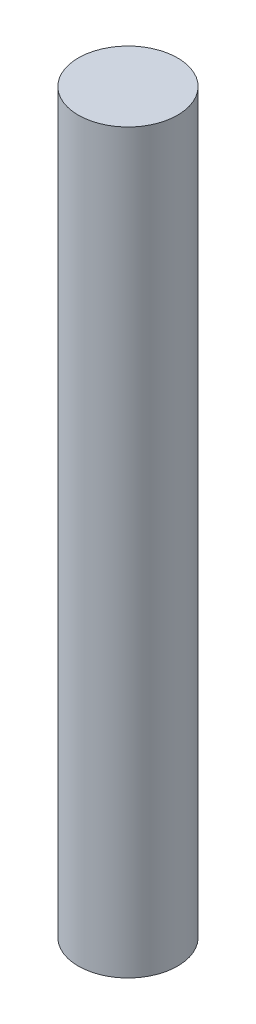
SolidWorks part; units mm, degrees
ref_plane "Front Plane" through (0, 0, 0) normal (0, 0, 1) x (1, 0, 0)
ref_plane "Top Plane" through (0, 0, 0) normal (0, 1, 0) x (1, 0, 0)
ref_plane "Right Plane" through (0, 0, 0) normal (1, 0, 0) x (0, 0, -1)
sketch "Sketch1" plane through (0, 0, 0) normal (0, 1, 0) x (1, 0, 0)
  circle A0 centre (0, 0) radius 27
  dimension "D1" = 54
extrude "Boss-Extrude1" add sketch "Sketch1" along normal blind 401
equation "\"Motor_Length\" = 401mm"
equation "\"Motor_OD\" = 54mm"
equation "\"D1@Sketch1\"=\"Motor_OD\""
equation "\"D1@Boss-Extrude1\"=\"Motor_Length\""
equation "\"Aft_Section_Length\" = 32in"
equation "\"Mid_Coupler_Length\" = 12in"
equation "\"AB_Coupler_OD_Length\"= 1in"
equation "\"AB_Coupling_Section_Length\"= 0.375in"
equation "\"AB_Coupler_Length\"= \"AB_Coupler_OD_Length\" + \"AB_Coupling_Section_Length\" * 2"
equation "\"Cutout_Angle\" = 60"
equation "\"AB_Paddle_Height\" = 0.375in"
equation "\"AB_Coupler_Num_Screws\"= 4"
equation "\"Num_Cutouts\" = 4"
equation "\"AB_Coupler_OD\"= 4.024in"
equation "\"AB_Coupler_ID\"= 3.7in"
equation "\"AB_Coupler_Surface_Diameter\"= 3.899in"
equation "\"AB_Coupling_Screw_Diameter\"= 0.1065in"
equation "\"AB_Central_Bushing_Length\" = 0.75in"
equation "\"Lead_Screw_Dist\" = 2in"
equation "\"Lead_Screw_Diam\" = 0.375in"
equation "\"Lead_Screw_Length\" = \"Mid_Coupler_Length\" + 2*0.375in + 2*0.5in"
equation "\"Paddle_Pin_Offset\" = 0.25in"
equation "\"Paddle_Pin_Radius\" = 2.25*2/3in"
equation "\"Paddle_Gear_OD\" = 3.2in"
equation "\"Fwd_BKHD_From_Top\" = 18in"
equation "\"Body_Tube_OD\"= 4.024in"
equation "\"Body_Tube_ID\"= 3.90in"
equation "\"Coupler_OD\" = 3.899in"
equation "\"Coupler_ID\" = 3.755in"
equation "\"Fwd_Section_Length\" = 20in"
equation "\"Mid_Section_Length\" = 4in"
equation "\"Aft_Upper_Tube_Length\" = 10in"
equation "\"Aft_Lower_Tube_Length\" = 18in"
equation "\"Nosecone_Coupler_Length\" = 5in"
equation "\"Avionics_Bulkhead_Thickness\" = 0.25in"
equation "\"Avionics_Bulkhead_Lip\" = 0.125in"
equation "\"Avionics_Board_Length\" = \"Mid_Coupler_Length\" - 2*\"Avionics_Bulkhead_Lip\""
equation "\"Lead_Screw_Hole_Diam\" = 0.386in"
equation "\"Centering_Ring_Cutout_Dia\"=1.5in"
